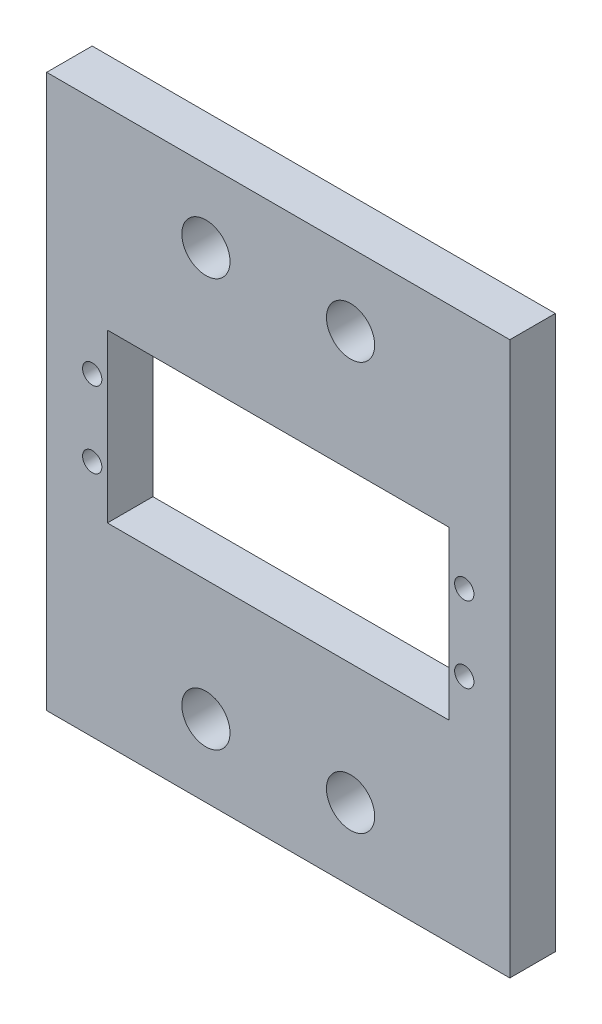
SolidWorks part; units mm, degrees
ref_plane "Front Plane" through (0, 0, 0) normal (0, 0, 1) x (1, 0, 0)
ref_plane "Top Plane" through (0, 0, 0) normal (0, 1, 0) x (1, 0, 0)
ref_plane "Right Plane" through (0, 0, 0) normal (1, 0, 0) x (0, 0, -1)
sketch "Sketch1" plane through (0, 0, 0) normal (0, 0, 1) x (1, 0, 0)
  line L0 (22.5, 22) -> (22.5, 0) construction
  line L1 (0, 0) -> (45, 0)
  line L2 (0, 0) -> (0, 22)
  line L3 (0, 22) -> (45, 22)
  line L4 (45, 0) -> (45, 22)
  line L5 (0, 11) -> (45, 11) construction
  line L7 (-8, 47.4) -> (53, 47.4)
  line L8 (-8, 47.4) -> (-8, -25.4)
  line L9 (-8, -25.4) -> (53, -25.4)
  line L10 (53, 47.4) -> (53, -25.4)
  circle A0 centre (-2, 16) radius 1.27
  circle A1 centre (-2, 6) radius 1.27
  circle A2 centre (47, 16) radius 1.27
  circle A3 centre (47, 6) radius 1.27
  circle A4 centre (12.975, -15.875) radius 3.175
  circle A5 centre (12.975, 37.875) radius 3.175
  circle A6 centre (32.025, 37.875) radius 3.175
  circle A7 centre (32.025, -15.875) radius 3.175
  dimension "D3" = 2.54
  dimension "D4" = 49
  dimension "D5" = 10
  dimension "D12" = 6.35
  dimension "D1" = 22
  dimension "D2" = 45
  dimension "D6" = 49
  dimension "D7" = 10
  dimension "D8" = 8
  dimension "D9" = 8
  dimension "D10" = 25.4
  dimension "D11" = 25.4
  dimension "D13" = 15.875
  dimension "D14" = 15.875
  dimension "D15" = 19.05
  dimension "D16" = 9.525
  dimension "D17" = 53.75
  dimension "D18" = 26.875
extrude "Boss-Extrude1" add sketch "Sketch1" along normal blind 5.9944
